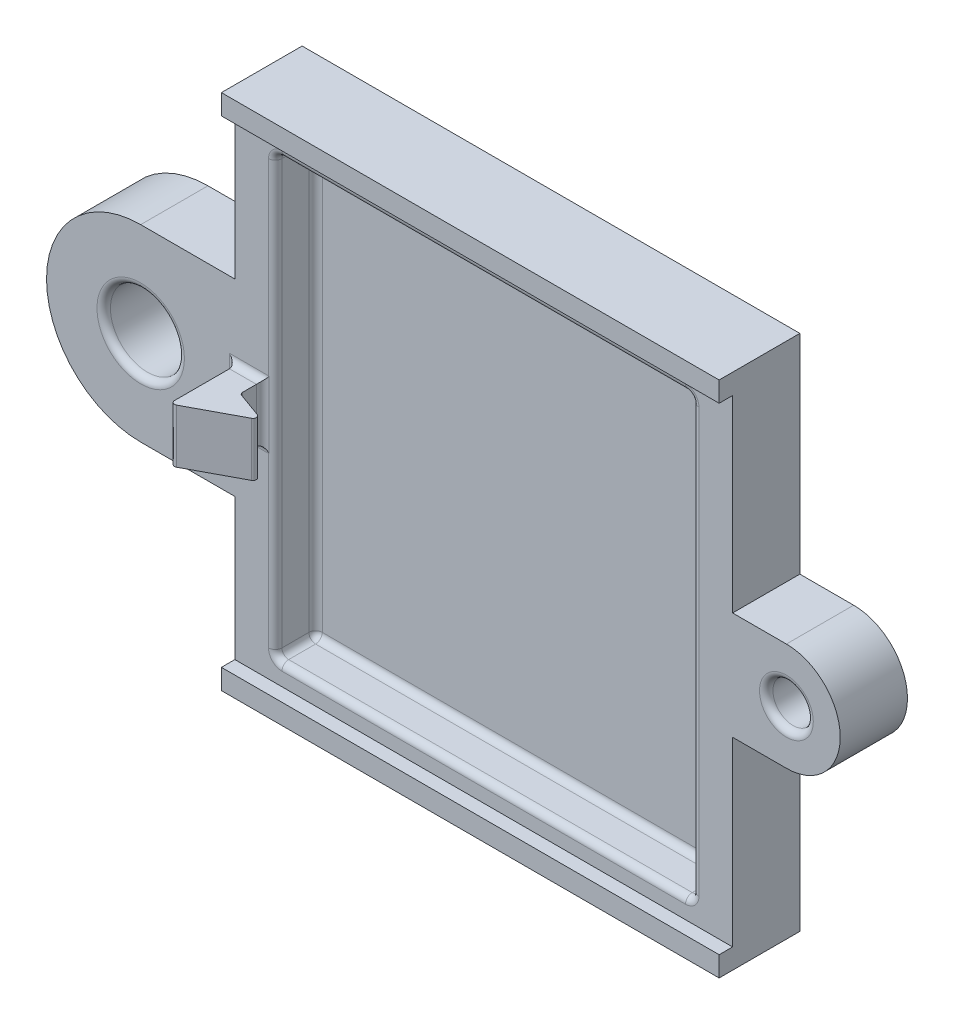
SolidWorks part; units mm, degrees
ref_plane "Front Plane" through (0, 0, 0) normal (1, 0, 0) x (0, 1, 0)
ref_plane "Top Plane" through (0, 0, 0) normal (0, 0, 1) x (0, 1, 0)
ref_plane "Right Plane" through (0, 0, 0) normal (0, 1, 0) x (-1, 0, 0)
sketch "Sketch1" plane through (0, 0, 0) normal (0, 0, 1) x (0, 1, 0)
  line L0 (-17.0192, 21.387) -> (17.4808, 21.387) construction
  line L1 (-19.0192, 23.887) -> (19.4808, 23.887)
  line L2 (-19.0192, 23.887) -> (-19.0192, -13.113)
  line L3 (-19.0192, -13.113) -> (19.4808, -13.113)
  line L4 (19.4808, 23.887) -> (19.4808, -13.113)
  line L5 (17.4808, 21.387) -> (17.4808, -10.613) construction
  line L6 (17.4808, -10.613) -> (-17.0192, -10.613) construction
  line L7 (-17.0192, -10.613) -> (-17.0192, 21.387) construction
  dimension "D1" = 2.5
  dimension "D2" = 2
  dimension "D3" = 2.5
  dimension "D4" = 2
extrude "Boss-Extrude1" add sketch "Sketch1" along normal blind 5
sketch "Sketch2" plane through (0, 0, 5) normal (0, 0, 1) x (1, 0, 0)
  line L0 (-23.887, 19.4808) -> (-23.887, -19.0192) construction
  line L1 (-20.887, 16.4808) -> (10.113, 16.4808)
  line L2 (-20.887, 16.4808) -> (-20.887, -16.0192)
  line L3 (-20.887, -16.0192) -> (10.113, -16.0192)
  line L4 (10.113, 16.4808) -> (10.113, -16.0192)
  line L5 (-23.887, -19.0192) -> (13.113, -19.0192) construction
  line L6 (13.113, -19.0192) -> (13.113, 19.4808) construction
  line L7 (13.113, 19.4808) -> (-23.887, 19.4808) construction
  dimension "D1" = 3
  dimension "D2" = 3
  dimension "D3" = 3
  dimension "D4" = 3
extrude "Cut-Extrude1" cut sketch "Sketch2" against normal blind 3
sketch "Sketch9" plane through (0, 0, 0) normal (0, 0, -1) x (1, 0, 0)
  line L0 (-23.887, 19.0192) -> (13.113, 19.0192) construction
  line L1 (17.113, 4.0192) -> (13.113, 4.0192)
  line L2 (-23.887, -19.4808) -> (-23.887, 19.0192) construction
  line L3 (13.113, 19.0192) -> (13.113, -19.4808) construction
  line L4 (-30.887, 7.0192) -> (-23.887, 7.0192)
  line L5 (-23.887, 7.0192) -> (-23.887, -6.9808)
  line L6 (-23.887, -6.9808) -> (-30.887, -6.9808)
  line L11 (13.113, -3.9808) -> (17.113, -3.9808)
  line L13 (13.113, 4.0192) -> (13.113, -3.9808)
  circle A0 centre (-30.887, 0.0192) radius 2.75
  circle A1 centre (17.113, 0.0192) radius 1.5
  arc A3 (-30.887, 7.0192) -> (-30.887, -6.9808) centre (-30.887, 0.0192) ccw
  arc A5 (17.113, -3.9808) -> (17.113, 4.0192) centre (17.113, 0.0192) ccw
  dimension "D1" = 5.5
  dimension "D2" = 3
  dimension "D3" = 19
  dimension "D4" = 19
  dimension "D5" = 7
  dimension "D6" = 4
extrude "Boss-Extrude4" add sketch "Sketch9" against normal blind 5
sketch "Sketch10" plane through (0, 0, 5) normal (0, 0, 1) x (1, 0, 0)
  line L0 (13.113, 3.9808) -> (13.113, 19.4808) construction
  line L1 (-23.887, 19.4808) -> (13.113, 19.4808)
  line L2 (-23.887, 19.4808) -> (-23.887, 17.9808)
  line L3 (-23.887, 17.9808) -> (13.113, 17.9808)
  line L4 (13.113, 19.4808) -> (13.113, 17.9808)
  line L5 (13.113, -19.0192) -> (13.113, -4.0192) construction
  line L6 (-23.887, -19.0192) -> (13.113, -19.0192)
  line L7 (-23.887, -19.0192) -> (-23.887, -17.5192)
  line L8 (-23.887, -17.5192) -> (13.113, -17.5192)
  line L9 (13.113, -19.0192) -> (13.113, -17.5192)
  dimension "D1" = 1.5
  dimension "D2" = 1.5
extrude "Boss-Extrude5" add sketch "Sketch10" along normal blind 1
sketch "Sketch12" plane through (0, 0, 0) normal (0, 1, 0) x (-1, 0, 0)
  line L7 (21.787, 6.5243) -> (21.787, 5)
  line L8 (21.787, 5) -> (23.787, 5)
  line L9 (23.787, 5) -> (23.787, 9.5833)
  line L12 (19.8169, 7.4092) -> (21.6216, 6.7595)
  line L13 (23.887, 6) -> (23.887, 0) construction
  line L14 (19.7839, 7.865) -> (23.4193, 9.8039)
  line L16 (30.887, 5) -> (23.887, 5) construction
  arc A0 (19.7839, 7.865) -> (19.8169, 7.4092) centre (19.9016, 7.6445) ccw
  arc A1 (21.787, 6.5243) -> (21.6216, 6.7595) centre (21.537, 6.5243) ccw
  arc A2 (23.787, 9.5833) -> (23.4193, 9.8039) centre (23.537, 9.5833) ccw
  point P21 (19.287, 7.6)
  point P24 (21.787, 6.7)
  point P27 (23.787, 10)
  dimension "D13" = 0.25
  dimension "D14" = 0.25
  dimension "D15" = 0.25
  dimension "D7" = 0.1
  dimension "D8" = 2
  dimension "D9" = 1.7
  dimension "D10" = 2.6
  dimension "D11" = 5
  dimension "D12" = 4.5
extrude "Boss-Extrude7" add sketch "Sketch12" along normal blind 1.5 and the other way blind 2.5
fillet "Fillet2" radius 0.5 1 edges at (15.613, -0.0192, 5)
fillet "Fillet4" radius 0.5 12 edges at (-5.387, 16.4808, 5) (-5.387, 16.4808, 2) (10.113, 0.2308, 2) (10.113, 16.4808, 3.5) (10.113, 0.2308, 5) (-5.387, -16.0192, 5) (10.113, -16.0192, 3.5) (-5.387, -16.0192, 2) (-20.887, -16.0192, 3.5) (-20.887, 0.2308, 2) (-20.887, 16.4808, 3.5) (-20.887, 0.2308, 5)
fillet "Fillet7" radius 0.5 4 edges at (-22.787, 1.5, 5) (-23.787, -0.5, 5) (-22.787, -2.5, 5) (-21.787, -0.5, 5)
fillet "Fillet10" radius 0.5 1 edges at (-33.637, -0.0192, 5)
fillet "Fillet11" radius 0.5 1 edges at (15.613, -0.0192, 0)
fillet "Fillet12" radius 0.5 1 edges at (-33.637, -0.0192, 0)
